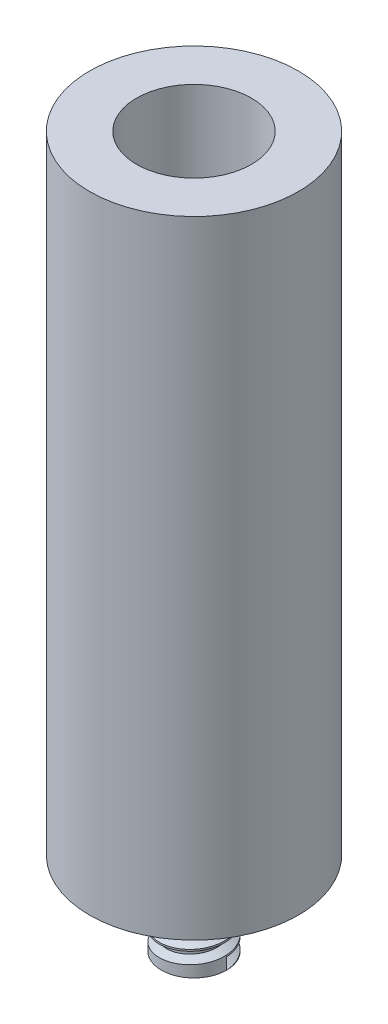
SolidWorks part; units mm, degrees
ref_plane "Plan de face" through (0, 0, 0) normal (0, 0, 1) x (1, 0, 0)
ref_plane "Plan de dessus" through (0, 0, 0) normal (0, 1, 0) x (1, 0, 0)
ref_plane "Plan de droite" through (0, 0, 0) normal (1, 0, 0) x (0, 0, -1)
sketch "Esquisse1" plane through (0, 0, 0) normal (0, 0, 1) x (1, 0, 0)
  line L0 (0, 0) -> (0, 8)
  line L1 (0, 8) -> (-6.875, 8)
  line L2 (-6.875, 8) -> (-6.875, 68)
  line L5 (3.125, 0) -> (0, 0)
  line L6 (3.125, 0) -> (3.125, 23)
  line L7 (3.125, 23) -> (-2.375, 23)
  line L8 (-2.375, 23) -> (-2.375, 68)
  line L9 (-2.375, 68) -> (-6.875, 68)
  dimension "D1" = 3.125
  dimension "D2" = 5.5
  dimension "D3" = 23
  dimension "D4" = 8
  dimension "D5" = 68
  dimension "D6" = 10
revolve "V1" add sketch "Esquisse1" angle 360 about L6
thread "Filetage1" pitch 1.27 start angle 0, offset 0, length 0, pitch 1.27, diameter 6.25
ref_plane "Plan1" through (6.25, 0, 0) normal (0, 0, 1) x (1, 0, 0)
sketch "Profil de filetage1" plane through (6.25, 0, 0) normal (0, 0, 1) x (1, 0, 0)
  line L0 (0, 0) -> (0, 1.27) construction
  line L11 (0, 0) -> (0, 1.1112)
  line L12 (0, 1.1112) -> (-0.6874, 0.7144)
  line L13 (-0.6874, 0.7144) -> (-0.6874, 0.3969)
  line L15 (-0.6874, 0.3969) -> (0, 0)
  line L17 (-0.6874, 0.5556) -> (0, 0.5556) construction
  point P2 (0, 0)
  dimension "Pitch" = 1.27
  dimension "Profile_Angle" = 60
  dimension "Profile_Land" = 0.3175
  dimension "Profile_Height" = 0.6874
sketch "Esquisse3" [suppressed] plane through (0, 0, 0) normal (0, 0, 1) x (1, 0, 0)
  line L0 (0, 0) -> (0, 8)
  line L1 (0, 8) -> (-3.875, 8)
  line L3 (-19.952, 68) -> (-2.375, 68)
  line L5 (3.125, 0) -> (0, 0)
  line L6 (3.125, 0) -> (3.125, 23)
  line L7 (3.125, 23) -> (-2.375, 23)
  line L8 (-2.375, 23) -> (-2.375, 68)
  line L9 (-3.875, 8) -> (-19.952, 68)
  dimension "D1" = 105
  dimension "D2" = 3.125
  dimension "D3" = 7
  dimension "D4" = 45
  dimension "D5" = 23
  dimension "D6" = 8
  dimension "D7" = 5.5
revolve "V2" [suppressed] add sketch "Esquisse3" angle 360 about L6
thread "Filetage2" [suppressed] pitch 1.27 start angle 0, offset 0, length 0, pitch 1.27, diameter 6.25
ref_plane "Plan2" through (6.25, 0, 0) normal (0, 0, 1) x (1, 0, 0)
sketch "Profil de filetage2" plane through (6.25, 0, 0) normal (0, 0, 1) x (1, 0, 0)
  line L0 (0, 0) -> (0, 1.27) construction
  line L11 (0, 0) -> (0, 1.1112)
  line L12 (0, 1.1112) -> (-0.6874, 0.7144)
  line L13 (-0.6874, 0.7144) -> (-0.6874, 0.3969)
  line L15 (-0.6874, 0.3969) -> (0, 0)
  line L17 (-0.6874, 0.5556) -> (0, 0.5556) construction
  point P2 (0, 0)
  dimension "Pitch" = 1.27
  dimension "Profile_Angle" = 60
  dimension "Profile_Land" = 0.3175
  dimension "Profile_Height" = 0.6874
sketch "Esquisse4" [suppressed] plane through (0, 0, 0) normal (0, 0, 1) x (1, 0, 0)
  line L0 (10.125, 68) -> (-3.875, 68) construction
  line L1 (25.1927, 63) -> (3.125, 63)
  line L2 (25.1927, 63) -> (25.1927, 43)
  line L3 (25.1927, 43) -> (3.125, 43)
  line L4 (3.125, 63) -> (3.125, 43)
  dimension "D1" = 5
  dimension "D2" = 20
  dimension "D3" = 3.125
extrude "V3" [suppressed] cut sketch "Esquisse4" against normal through all both and the other way through all
sketch "Esquisse5" [suppressed] plane through (0, 0, 0) normal (0, 0, 1) x (1, 0, 0)
  line L0 (0, 0) -> (0, 8)
  line L1 (0, 8) -> (-9.575, 8)
  line L2 (0, 0) -> (3.125, 0)
  line L4 (-2.375, 68) -> (-9.575, 68)
  line L6 (3.125, 0) -> (3.125, 23)
  line L7 (3.125, 23) -> (-2.375, 23)
  line L8 (-2.375, 23) -> (-2.375, 68)
  line L9 (-5.375, 68) -> (-5.375, 8) construction
  arc A0 (-9.575, 68) -> (-9.575, 8) centre (-114.6179, 38) cw
  point P12 (0, 4)
  dimension "D7" = 8
  dimension "D1" = 12.7
  dimension "D2" = 68
  dimension "D3" = 45
  dimension "D4" = 3.125
  dimension "D5" = 5.5
  dimension "D6" = 3
revolve "V4" [suppressed] add sketch "Esquisse5" angle 360 about L6
thread "Filetage3" [suppressed] pitch 1.27 start angle 0, offset 0, length 0, pitch 1.27, diameter 6.25
ref_plane "Plan3" through (6.25, 0, 0) normal (0, 0, 1) x (1, 0, 0)
sketch "Profil de filetage3" plane through (6.25, 0, 0) normal (0, 0, 1) x (1, 0, 0)
  line L0 (0, 0) -> (0, 1.27) construction
  line L11 (0, 0) -> (0, 1.1112)
  line L12 (0, 1.1112) -> (-0.6874, 0.7144)
  line L13 (-0.6874, 0.7144) -> (-0.6874, 0.3969)
  line L15 (-0.6874, 0.3969) -> (0, 0)
  line L17 (-0.6874, 0.5556) -> (0, 0.5556) construction
  point P2 (0, 0)
  dimension "Pitch" = 1.27
  dimension "Profile_Angle" = 60
  dimension "Profile_Land" = 0.3175
  dimension "Profile_Height" = 0.6874
sketch "Esquisse6" [suppressed] plane through (0, 0, 0) normal (0, 1, 0) x (1, 0, 0)
  line L1 (-5.6986, -5.7323) -> (2.115, -7.8013)
  line L2 (2.115, -7.8013) -> (7.8136, -2.069)
  line L3 (7.8136, -2.069) -> (5.6986, 5.7323)
  line L4 (5.6986, 5.7323) -> (-2.115, 7.8013)
  line L5 (-2.115, 7.8013) -> (-7.8136, 2.069)
  line L6 (-7.8136, 2.069) -> (-5.6986, -5.7323)
  circle A0 centre (0, 0) radius 7 construction
  dimension "D1" = 14
extrude "V5" [suppressed] add sketch "Esquisse6" along normal blind 60
sketch "Esquisse7" [suppressed] plane through (0, 0, 0) normal (0, -1, 0) x (1, 0, 0)
  circle A0 centre (0, 0) radius 3.125
  dimension "D1" = 6.25
extrude "V5 ex" [suppressed] add sketch "Esquisse7" along normal blind 8
sketch "Esquisse8" [suppressed] plane through (0, 60, 0) normal (0, 1, 0) x (1, 0, 0)
  circle A0 centre (0, 0) radius 5.5
extrude "V5 enlev" [suppressed] cut sketch "Esquisse8" against normal blind 45
thread "Filetage4" [suppressed] pitch 1.27 start angle 0, offset 0, length 0, pitch 1.27, diameter 6.25
ref_plane "Plan4" through (3.125, -8, 0) normal (0, 0, 1) x (1, 0, 0)
sketch "Profil de filetage4" plane through (3.125, -8, 0) normal (0, 0, 1) x (1, 0, 0)
  line L0 (0, 0) -> (0, 1.27) construction
  line L11 (0, 0) -> (0, 1.1112)
  line L12 (0, 1.1112) -> (-0.6874, 0.7144)
  line L13 (-0.6874, 0.7144) -> (-0.6874, 0.3969)
  line L15 (-0.6874, 0.3969) -> (0, 0)
  line L17 (-0.6874, 0.5556) -> (0, 0.5556) construction
  point P2 (0, 0)
  dimension "Pitch" = 1.27
  dimension "Profile_Angle" = 60
  dimension "Profile_Land" = 0.3175
  dimension "Profile_Height" = 0.6874
sketch "Esquisse9" [suppressed] plane through (0, 0, 0) normal (0, 0, 1) x (1, 0, 0)
  line L38 (0, 0) -> (-3.175, 0)
  line L39 (-3.175, 0) -> (-3.175, 8)
  line L40 (-3.175, 8) -> (-12.7, 8)
  line L41 (-12.7, 8) -> (-12.7, 11.18)
  line L42 (-12.7, 11.18) -> (-11.1125, 11.18)
  line L43 (-11.1125, 11.18) -> (-11.1125, 14.36)
  line L44 (-11.1125, 14.36) -> (-9.525, 14.36)
  line L45 (-9.525, 14.36) -> (-9.525, 17.54)
  line L46 (-9.525, 17.54) -> (-7.9375, 17.54)
  line L51 (-7.9375, 17.54) -> (-7.9375, 20.72)
  line L52 (-6.35, 23.9) -> (-7.9375, 23.9)
  line L53 (-7.9375, 23.9) -> (-7.9375, 27.08)
  line L54 (-7.9375, 27.08) -> (-9.525, 27.08)
  line L55 (-9.525, 27.08) -> (-9.525, 30.26)
  line L56 (-9.525, 30.26) -> (-11.1125, 30.26)
  line L57 (-7.9375, 20.72) -> (-6.35, 20.72)
  line L58 (-6.35, 20.72) -> (-6.35, 23.9)
  line L59 (-11.1125, 30.26) -> (-11.1125, 33.44)
  line L64 (-11.1125, 33.44) -> (-9.525, 33.44)
  line L65 (-9.525, 33.44) -> (-9.525, 36.62)
  line L66 (-9.525, 36.62) -> (-7.9375, 36.62)
  line L67 (-7.9375, 36.62) -> (-7.9375, 39.8)
  line L68 (-7.9375, 39.8) -> (-6.35, 39.8)
  line L69 (-6.35, 39.8) -> (-6.35, 42.98)
  line L70 (-6.35, 42.98) -> (-7.9375, 42.98)
  line L71 (-7.9375, 42.98) -> (-7.9375, 46.16)
  line L72 (-7.9375, 46.16) -> (-9.525, 46.16)
  line L73 (-9.525, 46.16) -> (-9.525, 49.34)
  line L74 (-9.525, 49.34) -> (-11.1125, 49.34)
  line L75 (-11.1125, 49.34) -> (-11.1125, 52.52)
  line L76 (-11.1125, 52.52) -> (-12.7, 52.52)
  line L77 (-12.7, 52.52) -> (-12.7, 55.7)
  line L81 (0, 0) -> (0, 21.4578)
  line L82 (0, 21.4578) -> (-5.5, 21.4578)
  line L83 (-5.5, 21.4578) -> (-5.5, 55.7)
  line L84 (-5.5, 55.7) -> (-12.7, 55.7)
  dimension "D1" = 3.18
  dimension "D2" = 8
  dimension "D3" = 3.175
  dimension "D4" = 1.5875
  dimension "D5" = 12.7
  dimension "D6" = 5.5
revolve "V6" [suppressed] add sketch "Esquisse9" angle 360 about L81
thread "Filetage5" [suppressed] pitch 1.27 start angle 0, offset 0, length 0, pitch 1.27, diameter 6.35
ref_plane "Plan5" through (3.175, 0, 0) normal (0, 0, 1) x (1, 0, 0)
sketch "Profil de filetage5" plane through (3.175, 0, 0) normal (0, 0, 1) x (1, 0, 0)
  line L0 (0, 0) -> (0, 1.27) construction
  line L11 (0, 0) -> (0, 1.1112)
  line L12 (0, 1.1112) -> (-0.6874, 0.7144)
  line L13 (-0.6874, 0.7144) -> (-0.6874, 0.3969)
  line L15 (-0.6874, 0.3969) -> (0, 0)
  line L17 (-0.6874, 0.5556) -> (0, 0.5556) construction
  point P2 (0, 0)
  dimension "Pitch" = 1.27
  dimension "Profile_Angle" = 60
  dimension "Profile_Land" = 0.3175
  dimension "Profile_Height" = 0.6874
sketch "Esquisse10" [suppressed] plane through (0, 0, 0) normal (0, 0, 1) x (1, 0, 0)
  line L0 (0, 0) -> (-3.175, 0)
  line L1 (-3.175, 0) -> (-3.175, 8)
  line L2 (-3.175, 8) -> (-12.7, 8)
  line L3 (-12.7, 8) -> (-12.7, 11.175)
  line L4 (-12.7, 11.175) -> (-12.7, 64.825) construction
  line L5 (-12.7, 64.825) -> (-12.7, 68)
  line L8 (0, 23) -> (-5.5, 23)
  line L9 (-5.5, 23) -> (-5.5, 68)
  line L10 (0, 0) -> (0, 23)
  line L11 (-5.5, 68) -> (-12.7, 68)
  line L12 (-12.7, 11.175) -> (-7.7, 11.175) construction
  line L13 (-7.7, 11.175) -> (-7.7, 64.825) construction
  line L14 (-7.7, 64.825) -> (-12.7, 64.825) construction
  arc A0 (-12.7, 11.175) -> (-12.7, 38) centre (-28.1895, 24.5875) ccw
  arc A1 (-12.7, 38) -> (-12.7, 64.825) centre (-28.1895, 51.4125) ccw
  dimension "D1" = 3.175
  dimension "D2" = 12.7
  dimension "D3" = 8
  dimension "D4" = 60
  dimension "D5" = 5.5
  dimension "D6" = 45
  dimension "D7" = 5
revolve "V7" [suppressed] add sketch "Esquisse10" angle 360 about L10
thread "Filetage6" [suppressed] pitch 1.27 start angle 0, offset 0, length 0, pitch 1.27, diameter 6.35
ref_plane "Plan6" through (3.175, 0, 0) normal (0, 0, 1) x (1, 0, 0)
sketch "Profil de filetage6" plane through (3.175, 0, 0) normal (0, 0, 1) x (1, 0, 0)
  line L0 (0, 0) -> (0, 1.27) construction
  line L11 (0, 0) -> (0, 1.1112)
  line L12 (0, 1.1112) -> (-0.6874, 0.7144)
  line L13 (-0.6874, 0.7144) -> (-0.6874, 0.3969)
  line L15 (-0.6874, 0.3969) -> (0, 0)
  line L17 (-0.6874, 0.5556) -> (0, 0.5556) construction
  point P2 (0, 0)
  dimension "Pitch" = 1.27
  dimension "Profile_Angle" = 60
  dimension "Profile_Land" = 0.3175
  dimension "Profile_Height" = 0.6874
